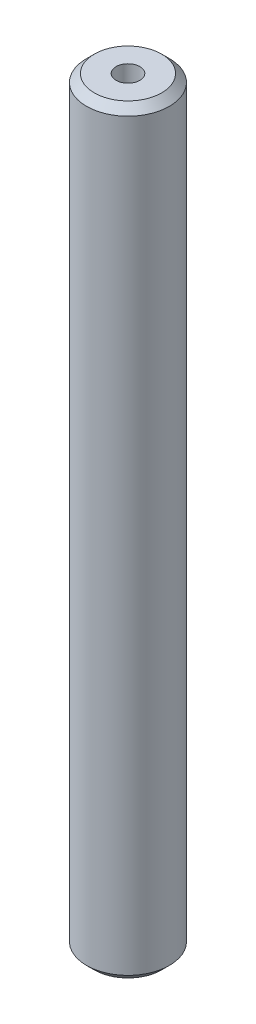
SolidWorks part; units mm, degrees
ref_plane "Front Plane" through (0, 0, 0) normal (0, 0, 1) x (1, 0, 0)
ref_plane "Top Plane" through (0, 0, 0) normal (0, 1, 0) x (1, 0, 0)
ref_plane "Right Plane" through (0, 0, 0) normal (1, 0, 0) x (0, 0, -1)
sketch "Sketch1" plane through (0, 0, 0) normal (0, 1, 0) x (1, 0, 0)
  circle A0 centre (0, 0) radius 30
  dimension "SHAFT_OD" = 60
extrude "Boss-Extrude1" add sketch "Sketch1" along normal blind 550.3205
sketch "Sketch2" plane through (0, 0, 0) normal (0, 1, 0) x (1, 0, 0)
  circle A0 centre (0, 0) radius 8.6383
  dimension "BORE_D" = 17.2767
extrude "Cut-Extrude1" cut sketch "Sketch2" along normal through all
chamfer "Chamfer1" distance 5.6162 angle 45 2 edges at (0, 550.3205, 30) (0, 0, 30)
